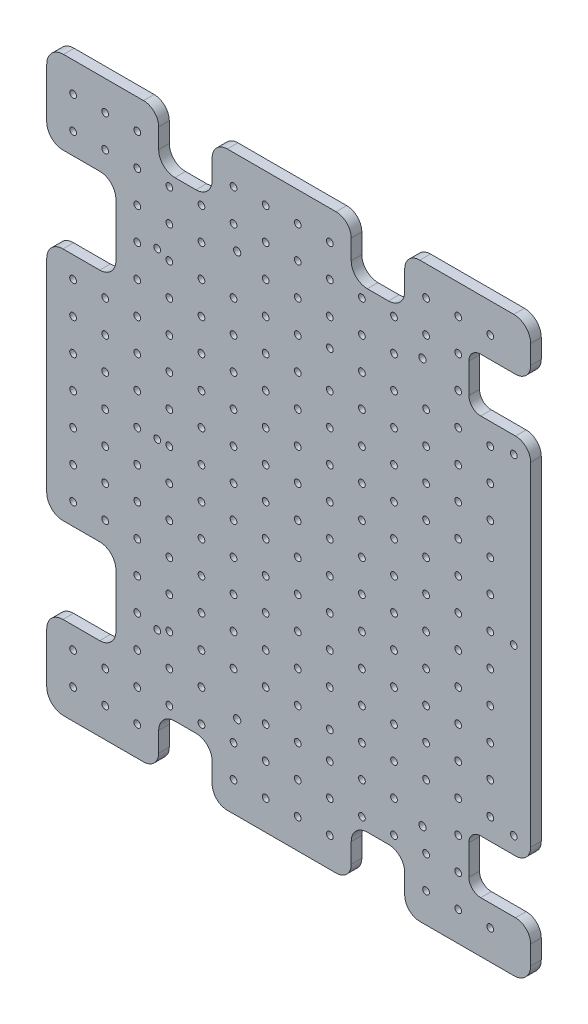
SolidWorks part; units mm, degrees
ref_plane "Front Plane" through (0, 0, 0) normal (0, 0, 1) x (1, 0, 0)
ref_plane "Top Plane" through (0, 0, 0) normal (0, 1, 0) x (1, 0, 0)
ref_plane "Right Plane" through (0, 0, 0) normal (1, 0, 0) x (0, 0, -1)
sketch "Sketch1" plane through (0, 0, 0) normal (0, 0, 1) x (1, 0, 0)
  line L1 (-143.635, 170) -> (143.635, 170)
  line L2 (-143.635, 170) -> (-143.635, -170)
  line L3 (-143.635, -170) -> (143.635, -170)
  line L4 (143.635, 170) -> (143.635, -170)
  dimension "D1" = 287.27
  dimension "D2" = 340
  dimension "D3" = 170
  dimension "D4" = 143.635
extrude "Base_Plate-Extrude" add sketch "Sketch1" along normal blind 6.3
sketch "Sketch3" plane through (0, 0, 6.3) normal (0, 0, 1) x (1, 0, 0)
  line L0 (218.6774, 98) -> (-212.5391, 98) construction
  line L1 (218.7113, -98) -> (-212.5283, -98) construction
  line L2 (133.635, 226.7998) -> (133.635, -231.3038) construction
  line L3 (143.635, -170) -> (143.635, 170) construction
  line L4 (-78.025, 174.4237) -> (-78.025, -178.7911) construction
  line L5 (412.3614, 0) -> (1049.4297, 0) construction
  line L6 (79.415, 225.6084) -> (79.415, -232.4952) construction
  line L7 (-30.585, -232.4952) -> (-30.585, 225.6084) construction
  line L8 (95.7553, 120.25) -> (-187.2723, 120.25) construction
  line L9 (88.1602, -120.25) -> (-163.8184, -120.25) construction
  circle A0 centre (133.635, 98) radius 2
  circle A1 centre (24.415, 98) radius 2
  circle A2 centre (-78.025, 98) radius 2
  circle A3 centre (-78.025, -98) radius 2
  circle A4 centre (24.415, -98) radius 2
  circle A5 centre (133.635, -98) radius 2
  circle A8 centre (133.635, 0) radius 2
  circle A9 centre (-78.025, 0) radius 2
  circle A85 centre (79.415, -120.25) radius 2.15
  circle A86 centre (-30.585, -120.25) radius 2.15
  circle A87 centre (-30.585, 120.25) radius 2.15
  circle A88 centre (79.415, 120.25) radius 2.15
  dimension "D1" = 4
  dimension "D8" = 4
  dimension "D9" = 4
  dimension "D10" = 4
  dimension "D11" = 4
  dimension "D12" = 4
  dimension "D16" = 4
  dimension "D17" = 4
  dimension "D20" = 4.3
  dimension "D21" = 4.3
  dimension "D22" = 4.3
  dimension "D23" = 4.3
  dimension "D3" = 109.22
  dimension "D4" = 102.44
  dimension "D5" = 102.44
  dimension "D6" = 109.22
  dimension "D2" = 196
  dimension "D7" = 98
  dimension "D13" = 10
  dimension "D14" = 98
  dimension "D15" = 98
  dimension "D18" = 110
  dimension "D19" = 240.5
  dimension "D24" = 120.25
  dimension "D25" = 55
extrude "Plate_to_Plate_Mnt-Thru-Hole" cut sketch "Sketch3" against normal through all
sketch "Sketch4" plane through (0, 0, 6.3) normal (0, 0, 1) x (1, 0, 0)
  line L0 (283.705, 0) -> (-313.8392, 0) construction
  line L1 (143.635, -170) -> (143.635, 170) construction
  circle A0 centre (-70.835, 0) radius 2
  circle A1 centre (-78.025, 0) radius 2 construction
  circle A2 centre (-51.785, 0) radius 2
  circle A3 centre (-32.735, 0) radius 2
  circle A4 centre (-13.685, 0) radius 2
  circle A5 centre (5.365, 0) radius 2
  circle A6 centre (24.415, 0) radius 2
  circle A7 centre (43.465, 0) radius 2
  circle A8 centre (62.515, 0) radius 2
  circle A9 centre (81.565, 0) radius 2
  circle A10 centre (100.615, 0) radius 2
  circle A11 centre (119.665, 0) radius 2
  circle A12 centre (-70.835, 19.05) radius 2
  circle A13 centre (-51.785, 19.05) radius 2
  circle A14 centre (-32.735, 19.05) radius 2
  circle A15 centre (-13.685, 19.05) radius 2
  circle A16 centre (5.365, 19.05) radius 2
  circle A17 centre (24.415, 19.05) radius 2
  circle A18 centre (43.465, 19.05) radius 2
  circle A19 centre (62.515, 19.05) radius 2
  circle A20 centre (81.565, 19.05) radius 2
  circle A21 centre (100.615, 19.05) radius 2
  circle A22 centre (119.665, 19.05) radius 2
  circle A23 centre (-70.835, 38.1) radius 2
  circle A24 centre (-51.785, 38.1) radius 2
  circle A25 centre (-32.735, 38.1) radius 2
  circle A26 centre (-13.685, 38.1) radius 2
  circle A27 centre (5.365, 38.1) radius 2
  circle A28 centre (24.415, 38.1) radius 2
  circle A29 centre (43.465, 38.1) radius 2
  circle A30 centre (62.515, 38.1) radius 2
  circle A31 centre (81.565, 38.1) radius 2
  circle A32 centre (100.615, 38.1) radius 2
  circle A33 centre (119.665, 38.1) radius 2
  circle A34 centre (-70.835, 57.15) radius 2
  circle A35 centre (-51.785, 57.15) radius 2
  circle A36 centre (-32.735, 57.15) radius 2
  circle A37 centre (-13.685, 57.15) radius 2
  circle A38 centre (5.365, 57.15) radius 2
  circle A39 centre (24.415, 57.15) radius 2
  circle A40 centre (43.465, 57.15) radius 2
  circle A41 centre (62.515, 57.15) radius 2
  circle A42 centre (81.565, 57.15) radius 2
  circle A43 centre (100.615, 57.15) radius 2
  circle A44 centre (119.665, 57.15) radius 2
  circle A45 centre (-70.835, -19.05) radius 2
  circle A46 centre (-51.785, -19.05) radius 2
  circle A47 centre (-32.735, -19.05) radius 2
  circle A48 centre (-13.685, -19.05) radius 2
  circle A49 centre (5.365, -19.05) radius 2
  circle A50 centre (24.415, -19.05) radius 2
  circle A51 centre (43.465, -19.05) radius 2
  circle A52 centre (62.515, -19.05) radius 2
  circle A53 centre (81.565, -19.05) radius 2
  circle A54 centre (100.615, -19.05) radius 2
  circle A55 centre (119.665, -19.05) radius 2
  circle A56 centre (-70.835, -38.1) radius 2
  circle A57 centre (-51.785, -38.1) radius 2
  circle A58 centre (-32.735, -38.1) radius 2
  circle A59 centre (-13.685, -38.1) radius 2
  circle A60 centre (5.365, -38.1) radius 2
  circle A61 centre (24.415, -38.1) radius 2
  circle A62 centre (43.465, -38.1) radius 2
  circle A63 centre (62.515, -38.1) radius 2
  circle A64 centre (81.565, -38.1) radius 2
  circle A65 centre (100.615, -38.1) radius 2
  circle A66 centre (119.665, -38.1) radius 2
  circle A67 centre (-70.835, -57.15) radius 2
  circle A68 centre (-51.785, -57.15) radius 2
  circle A69 centre (-32.735, -57.15) radius 2
  circle A70 centre (-13.685, -57.15) radius 2
  circle A71 centre (5.365, -57.15) radius 2
  circle A72 centre (24.415, -57.15) radius 2
  circle A73 centre (43.465, -57.15) radius 2
  circle A74 centre (62.515, -57.15) radius 2
  circle A75 centre (81.565, -57.15) radius 2
  circle A76 centre (100.615, -57.15) radius 2
  circle A77 centre (119.665, -57.15) radius 2
  circle A78 centre (133.635, 0) radius 2 construction
  dimension "D1" = 7.19
  dimension "D2" = 4
  dimension "D4" = 11
  dimension "D3" = 4
  dimension "D5" = 4
extrude "Center_Perforation-Thru-Hole" cut sketch "Sketch4" against normal through all
sketch "Sketch6" plane through (0, 0, 6.3) normal (0, 0, 1) x (1, 0, 0)
  line L0 (-34.6497, 0) -> (-186.3903, 0) construction
  line L1 (81.565, -183.8925) -> (81.565, 197.7612) construction
  line L2 (119.665, -208.9594) -> (119.665, 225.074) construction
  line L3 (-70.835, -206.2107) -> (-70.835, 262.0393) construction
  line L4 (-32.735, 186.3499) -> (-32.735, -192.7852) construction
  circle A0 centre (-89.885, 0) radius 2
  circle A1 centre (-51.785, -95.25) radius 2
  circle A2 centre (-70.835, 0) radius 2 construction
  circle A3 centre (-70.835, -95.25) radius 2
  circle A4 centre (-108.935, 0) radius 2
  circle A5 centre (-127.985, 0) radius 2
  circle A6 centre (-89.885, 19.05) radius 2
  circle A7 centre (-108.935, 19.05) radius 2
  circle A8 centre (-127.985, 19.05) radius 2
  circle A9 centre (-89.885, 38.1) radius 2
  circle A10 centre (-108.935, 38.1) radius 2
  circle A11 centre (-127.985, 38.1) radius 2
  circle A12 centre (-89.885, 57.15) radius 2
  circle A13 centre (-108.935, 57.15) radius 2
  circle A14 centre (-127.985, 57.15) radius 2
  circle A15 centre (-89.885, 76.2) radius 2
  circle A16 centre (-108.935, 76.2) radius 2
  circle A17 centre (-127.985, 76.2) radius 2
  circle A18 centre (-89.885, 95.25) radius 2
  circle A19 centre (-108.935, 95.25) radius 2
  circle A20 centre (-127.985, 95.25) radius 2
  circle A21 centre (-89.885, 114.3) radius 2
  circle A22 centre (-108.935, 114.3) radius 2
  circle A23 centre (-127.985, 114.3) radius 2
  circle A24 centre (-89.885, 133.35) radius 2
  circle A25 centre (-108.935, 133.35) radius 2
  circle A26 centre (-127.985, 133.35) radius 2
  circle A27 centre (-89.885, 152.4) radius 2
  circle A28 centre (-108.935, 152.4) radius 2
  circle A29 centre (-127.985, 152.4) radius 2
  circle A30 centre (-89.885, -19.05) radius 2
  circle A31 centre (-108.935, -19.05) radius 2
  circle A32 centre (-127.985, -19.05) radius 2
  circle A33 centre (-89.885, -38.1) radius 2
  circle A34 centre (-108.935, -38.1) radius 2
  circle A35 centre (-127.985, -38.1) radius 2
  circle A36 centre (-89.885, -57.15) radius 2
  circle A37 centre (-108.935, -57.15) radius 2
  circle A38 centre (-127.985, -57.15) radius 2
  circle A39 centre (-89.885, -76.2) radius 2
  circle A40 centre (-108.935, -76.2) radius 2
  circle A41 centre (-127.985, -76.2) radius 2
  circle A42 centre (-89.885, -95.25) radius 2
  circle A43 centre (-108.935, -95.25) radius 2
  circle A44 centre (-127.985, -95.25) radius 2
  circle A45 centre (-89.885, -114.3) radius 2
  circle A46 centre (-108.935, -114.3) radius 2
  circle A47 centre (-127.985, -114.3) radius 2
  circle A48 centre (-89.885, -133.35) radius 2
  circle A49 centre (-108.935, -133.35) radius 2
  circle A50 centre (-127.985, -133.35) radius 2
  circle A51 centre (-89.885, -152.4) radius 2
  circle A52 centre (-108.935, -152.4) radius 2
  circle A53 centre (-127.985, -152.4) radius 2
  circle A54 centre (-51.785, -114.3) radius 2
  circle A55 centre (-70.835, -114.3) radius 2
  circle A56 centre (119.665, -76.2) radius 2
  circle A57 centre (100.615, -76.2) radius 2
  circle A58 centre (119.665, -57.15) radius 2 construction
  circle A59 centre (100.615, -57.15) radius 2 construction
  circle A60 centre (119.665, -95.25) radius 2
  circle A61 centre (100.615, -95.25) radius 2
  circle A62 centre (119.665, -114.3) radius 2
  circle A63 centre (100.615, -114.3) radius 2
  circle A64 centre (119.665, -133.35) radius 2
  circle A65 centre (100.615, -133.35) radius 2
  circle A66 centre (119.665, -152.4) radius 2
  circle A67 centre (100.615, -152.4) radius 2
  circle A68 centre (-51.785, -133.35) radius 2
  circle A69 centre (119.665, 76.2) radius 2
  circle A70 centre (100.615, 76.2) radius 2
  circle A71 centre (100.615, 57.15) radius 2 construction
  circle A72 centre (119.665, 57.15) radius 2 construction
  circle A73 centre (119.665, 95.25) radius 2
  circle A74 centre (100.615, 95.25) radius 2
  circle A75 centre (119.665, 114.3) radius 2
  circle A76 centre (100.615, 114.3) radius 2
  circle A77 centre (119.665, 133.35) radius 2
  circle A78 centre (100.615, 133.35) radius 2
  circle A79 centre (119.665, 152.4) radius 2
  circle A80 centre (100.615, 152.4) radius 2
  circle A81 centre (-70.835, 76.2) radius 2
  circle A82 centre (-51.785, 76.2) radius 2
  circle A83 centre (-70.835, -76.2) radius 2
  circle A84 centre (-51.785, -76.2) radius 2
  circle A85 centre (-70.835, 57.15) radius 2 construction
  circle A86 centre (-51.785, 57.15) radius 2 construction
  circle A87 centre (-70.835, -57.15) radius 2 construction
  circle A88 centre (-51.785, -57.15) radius 2 construction
  circle A89 centre (-51.785, 95.25) radius 2
  circle A90 centre (-70.835, 95.25) radius 2
  circle A91 centre (-51.785, 114.3) radius 2
  circle A92 centre (-70.835, 114.3) radius 2
  circle A93 centre (-51.785, 133.35) radius 2
  circle A94 centre (-70.835, 133.35) radius 2
  circle A95 centre (-51.785, 152.4) radius 2
  circle A96 centre (-70.835, 152.4) radius 2
  circle A97 centre (-70.835, -133.35) radius 2
  circle A98 centre (-51.785, -152.4) radius 2
  circle A99 centre (-70.835, -152.4) radius 2
  circle A100 centre (62.515, -152.4) radius 2
  circle A101 centre (81.565, -76.2) radius 2
  circle A103 centre (81.565, -152.4) radius 2
  circle A105 centre (81.565, 76.2) radius 2
  circle A107 centre (81.565, 152.4) radius 2
  circle A108 centre (81.565, 57.15) radius 2 construction
  circle A109 centre (62.515, -76.2) radius 2
  circle A110 centre (62.515, 76.2) radius 2
  circle A111 centre (62.515, 152.4) radius 2
  circle A112 centre (43.465, -152.4) radius 2
  circle A113 centre (43.465, -76.2) radius 2
  circle A114 centre (43.465, 76.2) radius 2
  circle A115 centre (43.465, 152.4) radius 2
  circle A116 centre (24.415, -152.4) radius 2
  circle A117 centre (24.415, -76.2) radius 2
  circle A118 centre (24.415, 76.2) radius 2
  circle A119 centre (24.415, 152.4) radius 2
  circle A120 centre (5.365, -152.4) radius 2
  circle A121 centre (5.365, -76.2) radius 2
  circle A122 centre (5.365, 76.2) radius 2
  circle A123 centre (5.365, 152.4) radius 2
  circle A124 centre (-13.685, -152.4) radius 2
  circle A125 centre (-13.685, -76.2) radius 2
  circle A126 centre (-13.685, 76.2) radius 2
  circle A127 centre (-13.685, 152.4) radius 2
  circle A128 centre (-32.735, -152.4) radius 2
  circle A129 centre (-32.735, -76.2) radius 2
  circle A130 centre (-32.735, 76.2) radius 2
  circle A131 centre (-32.735, 152.4) radius 2
  circle A132 centre (-51.785, -152.4) radius 2
  circle A133 centre (-51.785, -76.2) radius 2
  circle A134 centre (-51.785, 76.2) radius 2
  circle A135 centre (-51.785, 152.4) radius 2
  circle A136 centre (-70.835, -152.4) radius 2
  circle A137 centre (-70.835, -76.2) radius 2
  circle A138 centre (-70.835, 76.2) radius 2
  circle A139 centre (-70.835, 152.4) radius 2
  circle A140 centre (-89.885, -152.4) radius 2
  circle A141 centre (-89.885, -76.2) radius 2
  circle A142 centre (-89.885, 76.2) radius 2
  circle A143 centre (-89.885, 152.4) radius 2
  circle A144 centre (81.565, -133.35) radius 2
  circle A145 centre (-32.735, -133.35) radius 2
  circle A146 centre (5.365, -95.25) radius 2
  circle A147 centre (-13.685, -95.25) radius 2
  circle A148 centre (-32.735, -95.25) radius 2
  circle A149 centre (81.565, -95.25) radius 2
  circle A150 centre (62.515, -95.25) radius 2
  circle A151 centre (43.465, -95.25) radius 2
  circle A156 centre (-32.735, 95.25) radius 2
  circle A157 centre (-13.685, 95.25) radius 2
  circle A158 centre (5.365, 95.25) radius 2
  circle A159 centre (43.465, 95.25) radius 2
  circle A160 centre (62.515, 95.25) radius 2
  circle A161 centre (81.565, 95.25) radius 2
  circle A166 centre (62.515, 133.35) radius 2
  circle A167 centre (43.465, 133.35) radius 2
  circle A168 centre (24.415, 133.35) radius 2
  circle A169 centre (5.365, 133.35) radius 2
  circle A170 centre (-13.685, 133.35) radius 2
  circle A171 centre (62.515, 114.3) radius 2
  circle A172 centre (43.465, 114.3) radius 2
  circle A173 centre (24.415, 114.3) radius 2
  circle A174 centre (5.365, 114.3) radius 2
  circle A175 centre (-13.685, 114.3) radius 2
  circle A176 centre (62.515, -133.35) radius 2
  circle A177 centre (43.465, -133.35) radius 2
  circle A178 centre (24.415, -133.35) radius 2
  circle A179 centre (5.365, -133.35) radius 2
  circle A180 centre (-13.685, -133.35) radius 2
  circle A181 centre (62.515, -114.3) radius 2
  circle A182 centre (43.465, -114.3) radius 2
  circle A183 centre (24.415, -114.3) radius 2
  circle A184 centre (5.365, -114.3) radius 2
  circle A185 centre (-13.685, -114.3) radius 2
  circle A186 centre (81.565, 133.35) radius 2
  circle A187 centre (-32.735, 133.35) radius 2
  point P2 (-51.785, 0)
  point P3 (-70.835, 0)
  point P4 (81.565, -57.15)
  point P5 (-32.735, -57.15)
  point P6 (119.665, -57.15)
  point P166 (-70.835, -57.15)
  dimension "D1" = 4
  dimension "D2" = 19.05
  dimension "D3" = 3
  dimension "D4" = 9
  dimension "D6" = 19.05
  dimension "D7" = 19.05
  dimension "D8" = 19.05
  dimension "D9" = 4
  dimension "D10" = 4
  dimension "D12" = 19.05
  dimension "D13" = 19.05
  dimension "D14" = 19.05
  dimension "D15" = 4
  dimension "D16" = 4
  dimension "D18" = 19.05
  dimension "D19" = 19.05
  dimension "D20" = 19.05
  dimension "D21" = 19.05
  dimension "D22" = 19.05
  dimension "D23" = 19.05
  dimension "D24" = 4
  dimension "D25" = 4
  dimension "D26" = 4
  dimension "D27" = 4
  dimension "D30" = 19.05
  dimension "D31" = 76.2
  dimension "D32" = 76.2
  dimension "D33" = 4
  dimension "D34" = 10
  dimension "D35" = 4
  dimension "D36" = 19.05
  dimension "D37" = 19.05
  dimension "D38" = 4
  dimension "D39" = 4
  dimension "D40" = 4
  dimension "D41" = 4
  dimension "D42" = 19.05
  dimension "D47" = 4
  dimension "D48" = 19.05
  dimension "D49" = 4
  dimension "D50" = 19.05
  dimension "D5" = 9
  dimension "D11" = 5
  dimension "D17" = 5
  dimension "D28" = 5
  dimension "D29" = 5
  dimension "D43" = 2
  dimension "D45" = 2
  dimension "D44" = 3
  dimension "D46" = 3
extrude "Extended_Perforation-Thru-Hole" cut sketch "Sketch6" against normal through all
sketch "Sketch10" plane through (0, 0, 0) normal (0, 0, -1) x (-1, 0, 0)
  line L0 (-189.4299, 0) -> (209.3699, 0) construction
  line L1 (0, 228.4012) -> (0, -224.2923) construction
  line L2 (134.035, -69.85) -> (112.185, -69.85)
  line L3 (143.635, 170) -> (143.635, -170) construction
  line L4 (102.585, -79.45) -> (102.585, -111.05)
  line L5 (112.185, -120.65) -> (134.035, -120.65)
  line L7 (143.635, -130.25) -> (143.635, -162.3743) construction
  line L8 (143.635, -60.25) -> (143.635, -31.6818) construction
  line L9 (143.635, -130.25) -> (143.635, -60.25)
  line L10 (143.635, 60.25) -> (143.635, 31.6818) construction
  line L11 (143.635, 130.25) -> (143.635, 162.3743) construction
  line L12 (143.635, 130.25) -> (143.635, 60.25)
  line L13 (112.185, 120.65) -> (134.035, 120.65)
  line L14 (102.585, 79.45) -> (102.585, 111.05)
  line L15 (134.035, 69.85) -> (112.185, 69.85)
  line L16 (-143.635, -170) -> (-143.635, 170) construction
  line L17 (-113.965, 139.7) -> (-134.635, 139.7)
  line L18 (-106.965, 132.7) -> (-106.965, 114.95)
  line L19 (-113.965, 107.95) -> (-134.635, 107.95)
  line L21 (-143.635, 148.7) -> (-143.635, 158.7) construction
  line L22 (-143.635, 98.95) -> (-143.635, 88.95) construction
  line L23 (-143.635, -98.95) -> (-143.635, -88.95) construction
  line L24 (-143.635, -148.7) -> (-143.635, -158.7) construction
  line L25 (-113.965, -107.95) -> (-134.635, -107.95)
  line L26 (-106.965, -132.7) -> (-106.965, -114.95)
  line L27 (-113.965, -139.7) -> (-134.635, -139.7)
  line L28 (-143.635, 148.7) -> (-143.635, 98.95)
  line L29 (-143.635, -98.95) -> (-143.635, -148.7)
  line L30 (143.635, -170) -> (-143.635, -170) construction
  line L31 (-59.265, -139.7) -> (-46.715, -139.7)
  line L32 (-68.865, -149.3) -> (-68.865, -161)
  line L34 (-37.115, -149.3) -> (-37.115, -161)
  line L35 (-77.865, -170) -> (-87.865, -170) construction
  line L36 (-28.115, -170) -> (-18.115, -170) construction
  line L37 (36.435, -170) -> (26.435, -170) construction
  line L38 (55.035, -139.7) -> (67.585, -139.7)
  line L39 (45.435, -149.3) -> (45.435, -161)
  line L41 (77.185, -149.3) -> (77.185, -161)
  line L42 (86.185, -170) -> (96.185, -170) construction
  line L43 (-77.865, -170) -> (-28.115, -170)
  line L44 (36.435, -170) -> (86.185, -170)
  line L45 (86.185, 170) -> (96.185, 170) construction
  line L46 (36.435, 170) -> (26.435, 170) construction
  line L47 (-28.115, 170) -> (-18.115, 170) construction
  line L48 (-77.865, 170) -> (-87.865, 170) construction
  line L49 (36.435, 170) -> (86.185, 170)
  line L50 (-77.865, 170) -> (-28.115, 170)
  line L51 (77.185, 149.3) -> (77.185, 161)
  line L52 (45.435, 149.3) -> (45.435, 161)
  line L53 (55.035, 139.7) -> (67.585, 139.7)
  line L54 (-37.115, 149.3) -> (-37.115, 161)
  line L55 (-68.865, 149.3) -> (-68.865, 161)
  line L56 (-59.265, 139.7) -> (-46.715, 139.7)
  circle A0 centre (108.935, -114.3) radius 2 construction
  circle A1 centre (108.935, -76.2) radius 2 construction
  circle A2 centre (108.935, -95.25) radius 2 construction
  arc A3 (112.185, -69.85) -> (102.585, -79.45) centre (112.185, -79.45) ccw
  arc A4 (102.585, -111.05) -> (112.185, -120.65) centre (112.185, -111.05) ccw
  arc A5 (134.035, -120.65) -> (143.635, -130.25) centre (134.035, -130.25) cw
  arc A6 (134.035, -69.85) -> (143.635, -60.25) centre (134.035, -60.25) ccw
  arc A7 (134.035, 69.85) -> (143.635, 60.25) centre (134.035, 60.25) cw
  arc A8 (134.035, 120.65) -> (143.635, 130.25) centre (134.035, 130.25) ccw
  arc A9 (102.585, 111.05) -> (112.185, 120.65) centre (112.185, 111.05) cw
  arc A10 (112.185, 69.85) -> (102.585, 79.45) centre (112.185, 79.45) cw
  circle A11 centre (51.785, -152.4) radius 2 construction
  circle A12 centre (70.835, -152.4) radius 2 construction
  circle A13 centre (-100.615, 133.35) radius 2 construction
  arc A14 (-106.965, 114.95) -> (-113.965, 107.95) centre (-113.965, 114.95) cw
  arc A15 (-113.965, 139.7) -> (-106.965, 132.7) centre (-113.965, 132.7) cw
  arc A16 (-134.635, 107.95) -> (-143.635, 98.95) centre (-134.635, 98.95) ccw
  arc A17 (-134.635, 139.7) -> (-143.635, 148.7) centre (-134.635, 148.7) cw
  arc A18 (-134.635, -139.7) -> (-143.635, -148.7) centre (-134.635, -148.7) ccw
  arc A19 (-134.635, -107.95) -> (-143.635, -98.95) centre (-134.635, -98.95) cw
  arc A20 (-113.965, -139.7) -> (-106.965, -132.7) centre (-113.965, -132.7) ccw
  arc A21 (-106.965, -114.95) -> (-113.965, -107.95) centre (-113.965, -114.95) ccw
  circle A22 centre (-119.665, 133.35) radius 2 construction
  circle A23 centre (-119.665, 114.3) radius 2 construction
  circle A24 centre (-62.515, -152.4) radius 2 construction
  circle A25 centre (-43.465, -152.4) radius 2 construction
  circle A26 centre (-43.465, -133.35) radius 2 construction
  arc A27 (-59.265, -139.7) -> (-68.865, -149.3) centre (-59.265, -149.3) ccw
  arc A28 (-46.715, -139.7) -> (-37.115, -149.3) centre (-46.715, -149.3) cw
  arc A29 (-37.115, -161) -> (-28.115, -170) centre (-28.115, -161) ccw
  arc A30 (-68.865, -161) -> (-77.865, -170) centre (-77.865, -161) cw
  circle A31 centre (51.785, -133.35) radius 2 construction
  arc A32 (67.585, -139.7) -> (77.185, -149.3) centre (67.585, -149.3) cw
  arc A33 (55.035, -139.7) -> (45.435, -149.3) centre (55.035, -149.3) ccw
  arc A34 (36.435, -170) -> (45.435, -161) centre (36.435, -161) ccw
  arc A35 (77.185, -161) -> (86.185, -170) centre (86.185, -161) ccw
  arc A37 (77.185, 161) -> (86.185, 170) centre (86.185, 161) cw
  arc A38 (36.435, 170) -> (45.435, 161) centre (36.435, 161) cw
  arc A39 (55.035, 139.7) -> (45.435, 149.3) centre (55.035, 149.3) cw
  arc A40 (67.585, 139.7) -> (77.185, 149.3) centre (67.585, 149.3) ccw
  arc A41 (-68.865, 161) -> (-77.865, 170) centre (-77.865, 161) ccw
  arc A42 (-37.115, 161) -> (-28.115, 170) centre (-28.115, 161) cw
  arc A43 (-46.715, 139.7) -> (-37.115, 149.3) centre (-46.715, 149.3) ccw
  arc A44 (-59.265, 139.7) -> (-68.865, 149.3) centre (-59.265, 149.3) cw
  point P26 (143.635, -120.65)
  point P29 (143.635, -69.85)
  point P43 (143.635, 69.85)
  point P44 (143.635, 120.65)
  point P66 (-143.635, 107.95)
  point P86 (-143.635, -107.95)
  point P106 (-37.115, -170)
  point P128 (77.185, -170)
  point P155 (77.185, 170)
  point P156 (-37.115, 170)
  dimension "D13" = 10
  dimension "D4" = 9.6
  dimension "D5" = 9.6
  dimension "D9" = 7
  dimension "D10" = 9
  dimension "D17" = 9.6
  dimension "D18" = 9
  dimension "D25" = 9.6
  dimension "D26" = 9
  dimension "D1" = 6.35
  dimension "D2" = 6.35
  dimension "D3" = 6.35
  dimension "D8" = 6.35
  dimension "D11" = 9
  dimension "D12" = 10
  dimension "D6" = 6.35
  dimension "D7" = 6.35
  dimension "D14" = 6.35
  dimension "D15" = 6.35
  dimension "D16" = 6.35
  dimension "D19" = 10
  dimension "D20" = 10
  dimension "D21" = 11.7
  dimension "D22" = 6.35
  dimension "D23" = 6.35
  dimension "D24" = 6.35
  dimension "D27" = 11.7
  dimension "D28" = 10
  dimension "D29" = 10
extrude "Cable_Routing-Cutout" cut sketch "Sketch10" against normal through all
fillet "Fillet1" radius 10 4 edges at (-143.635, -170, 3.15) (-143.635, 170, 3.15) (143.635, 170, 3.15) (143.635, -170, 3.15)
equation "\"D3@Sketch1\"=\"D2@Sketch1\"/2"
equation "\"D4@Sketch1\"=\"D1@Sketch1\"/2"
equation "\"PLATE_LEN\"= 287.27"
equation "\"D1@Sketch1\"=\"PLATE_LEN\""
equation "\"PLATE_WID\"= 340"
equation "\"D2@Sketch1\"=\"PLATE_WID\""
equation "\"PLATE_THICKNESS\"=6.3"
equation "\"D1@Base_Plate-Extrude\" = \"PLATE_THICKNESS\""
equation "\"FRONT_TO_TRIPOD\"=110"
equation "\"TRIPOD_STRIDE\"=340"
equation "\"D7@Sketch3\"=\"D2@Sketch3\"/2"
equation "\"D14@Sketch3\"=\"D2@Sketch3\"/2"
equation "\"D15@Sketch3\"=\"D2@Sketch3\"/2"
equation "\"D24@Sketch3\"=\"D19@Sketch3\"/2"
equation "\"D25@Sketch3\"=\"D18@Sketch3\"/2"
equation "\"D1@Sketch10\"=19.05/3"
equation "\"D2@Sketch10\"=19.05/3"
equation "\"D3@Sketch10\"=19.05/3"
equation "\"D7@Sketch10\"=19.05/3"
